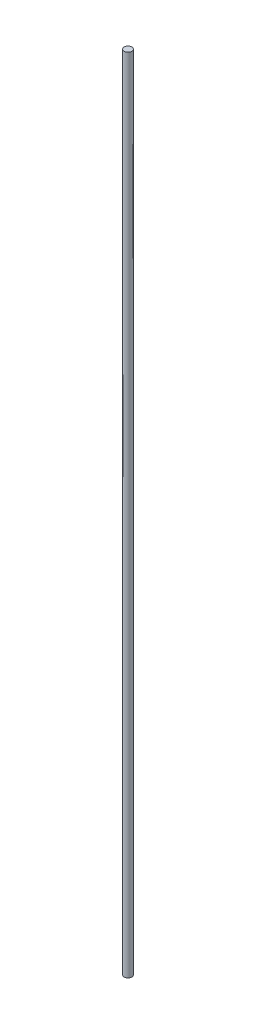
SolidWorks part; units mm, degrees
ref_plane "Front Plane" through (0, 0, 0) normal (0, 0, 1) x (1, 0, 0)
ref_plane "Top Plane" through (0, 0, 0) normal (0, 1, 0) x (1, 0, 0)
ref_plane "Right Plane" through (0, 0, 0) normal (1, 0, 0) x (0, 0, -1)
sketch "Sketch1" plane through (0, 0, 0) normal (0, 1, 0) x (1, 0, 0)
  circle A0 centre (0, 0) radius 0.825
  dimension "D1" = 1.65
extrude "Boss-Extrude1" add sketch "Sketch1" along normal blind 173
